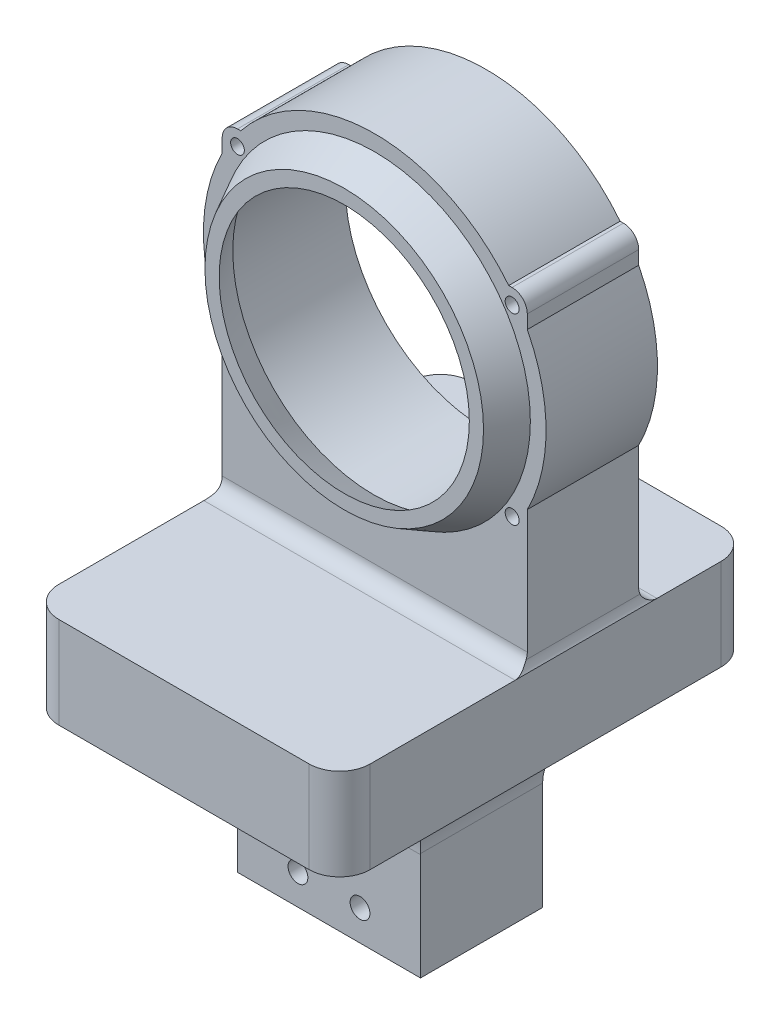
SolidWorks part; units mm, degrees
ref_plane "Alzado" through (0, 0, 0) normal (0, 0, 1) x (1, 0, 0)
ref_plane "Planta" through (0, 0, 0) normal (0, 1, 0) x (1, 0, 0)
ref_plane "Vista lateral" through (0, 0, 0) normal (1, 0, 0) x (0, 0, -1)
sketch "Croquis1" plane through (0, 0, 0) normal (0, 1, 0) x (1, 0, 0)
  line L1 (-51, 67.5) -> (51, 67.5)
  line L2 (-51, 67.5) -> (-51, -67.5)
  line L3 (-51, -67.5) -> (51, -67.5)
  line L4 (51, 67.5) -> (51, -67.5)
  line L5 (-51, 67.5) -> (51, -67.5) construction
  line L6 (-51, -67.5) -> (51, 67.5) construction
  point P0 (0, 0)
  dimension "D1" = 135
  dimension "D2" = 102
extrude "Saliente-Extruir1" add sketch "Croquis1" along normal blind 30
sketch "Croquis3" plane through (0, 0, 0) normal (0, 0, 1) x (1, 0, 0)
  line L0 (43.907, 136) -> (45, 136)
  line L1 (50, 75.4496) -> (50, 30)
  line L2 (0, 0) -> (0, 85.4991) construction
  line L10 (-45, 136) -> (-43.907, 136)
  line L11 (-50, 131) -> (-50, 126.5504)
  line L12 (-50, 30) -> (50, 30)
  line L13 (50, 131) -> (50, 126.5504)
  line L14 (-51, 30) -> (51, 30) construction
  line L15 (-50, 75.4496) -> (-50, 30)
  circle A0 centre (0, 101) radius 46.15
  circle A1 centre (0, 101) radius 56.15
  arc A2 (45, 136) -> (50, 131) centre (45, 131) cw
  arc A3 (-45, 136) -> (-50, 131) centre (-45, 131) ccw
  point P4 (0, 0)
  point P17 (50, 136)
  point P20 (-50, 136)
  point P22 (0, 0)
  dimension "D4" = 92.3
  dimension "D6" = 5
  dimension "D1" = 100
  dimension "D2" = 10
  dimension "D3" = 35
  dimension "D5" = 50
  dimension "D7" = 71
extrude "Saliente-Extruir2" add sketch "Croquis3" against normal blind 36.5 from offset 5 contours A1 L15 L12 | A1 L12 L1 | L10 A3 L11 A1 | A2 L0 A1 L13 | A1 | A0 region at (47.8302, 132.4886, 0) region at (-47.8302, 132.4886, 0) region at (0, 43.3281, 0)
sketch "Croquis5" plane through (0, 0, 5) normal (0, 0, 1) x (1, 0, 0)
  circle A0 centre (0, 101) radius 41
  circle A1 centre (0, 101) radius 51
  circle A2 centre (0, 101) radius 46.15 construction
  circle A3 centre (0, 101) radius 46.15 construction
  dimension "D1" = 82
  dimension "D2" = 10
extrude "Saliente-Extruir3" add sketch "Croquis5" along normal blind 10
chamfer "Chaflán1" distance 10 angle 28.15 1 edges at (41, 101, 5) first distance on face at (41, 101, 15)
chamfer "Chaflán2" distance 10 angle 28.15 1 edges at (51, 101, 15) first distance on face at (51, 101, 15)
fillet "Redondeo1" radius 5 4 edges at (0, 30, -31.5) (-50, 30, -13.25) (0, 30, 5) (50, 30, -13.25)
sketch "Croquis7" plane through (0, 0, -31.5) normal (0, 0, -1) x (-1, 0, 0)
  line L0 (0, 101) -> (71.2114, 101) construction
  line L1 (51, 30) -> (-51, 30) construction
  circle A0 centre (44.9882, 131.0136) radius 2.2483
  circle A1 centre (-45.0262, 131.0136) radius 2.2831
  circle A2 centre (-45.0262, 70.9864) radius 2.2831
  circle A3 centre (44.9882, 70.9864) radius 2.2483
  point P10 (0, 0)
  point P11 (0, 102.0521)
  dimension "D3" = 4.4965
  dimension "D1" = 30.0136
  dimension "D2" = 44.9882
  dimension "D4" = 71
extrude "Cortar-Extruir2" cut sketch "Croquis7" against normal through all
fillet "Redondeo2" radius 10 4 edges at (-51, 15, -67.5) (-51, 15, 67.5) (51, 15, -67.5) (51, 15, 67.5)
sketch "Croquis8" plane through (0, 0, 0) normal (0, -1, 0) x (1, 0, 0)
  line L0 (30, 20) -> (30, -20)
  line L1 (-20, 10) -> (20, 10)
  line L2 (-20, 10) -> (-20, -10)
  line L3 (-20, -10) -> (20, -10)
  line L4 (20, 10) -> (20, -10)
  line L5 (-20, 10) -> (20, -10) construction
  line L6 (-20, -10) -> (20, 10) construction
  line L7 (-30, -20) -> (30, -20)
  line L8 (-30, 20) -> (-30, -20)
  line L9 (-30, 20) -> (30, 20)
  point P0 (0, 0)
  point P10 (0, 0)
  dimension "D1" = 20
  dimension "D2" = 40
  dimension "D3" = 10
extrude "Saliente-Extruir4" add sketch "Croquis8" along normal blind 60
fillet "Redondeo3" radius 25 4 edges at (-30, 0, 0) (0, 0, -20) (0, 0, 20) (30, 0, 0)
sketch "Croquis9" plane through (0, 0, -20) normal (0, 0, -1) x (-1, 0, 0)
  line L0 (0, -60) -> (0, -33.4422) construction
  line L1 (30, -60) -> (-30, -60) construction
  line L2 (30, -42.5) -> (-9.4009, -42.5) construction
  line L3 (30, -60) -> (30, -25) construction
  line L4 (-30, -60) -> (-30, -25) construction
  circle A0 centre (-10.17, -50) radius 3.25
  circle A1 centre (10.17, -50) radius 3.25
  circle A2 centre (10.17, -35) radius 3.25
  circle A3 centre (-10.17, -35) radius 3.25
  dimension "D1" = 6.5
  dimension "D2" = 10
  dimension "D3" = 19.83
extrude "Cortar-Extruir3" cut sketch "Croquis9" against normal through all
